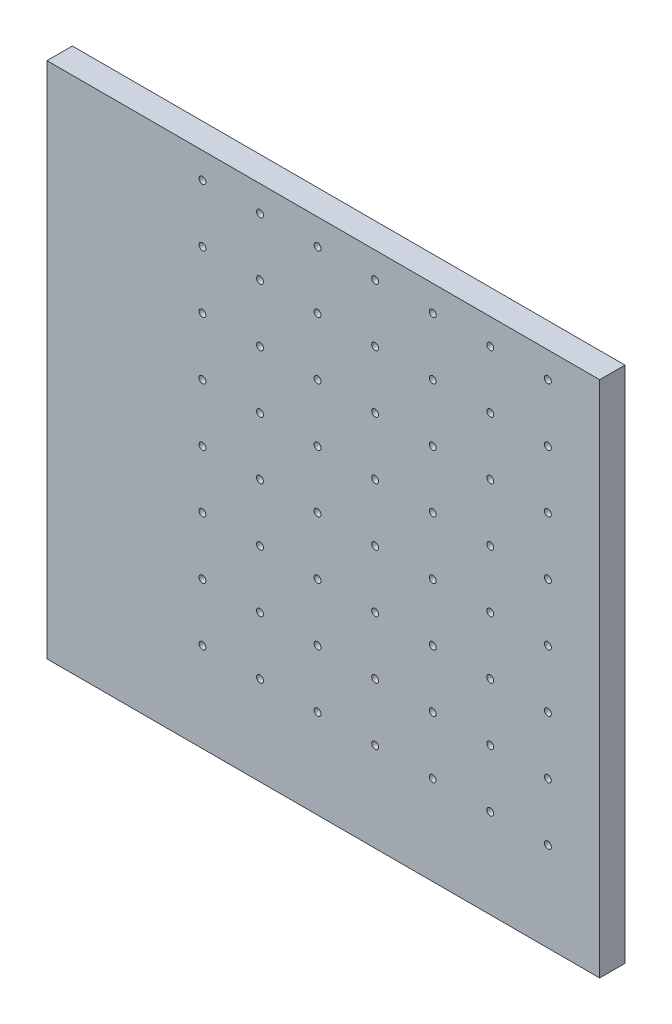
SolidWorks part; units mm, degrees
ref_plane "Front" through (0, 0, 0) normal (0, 0, 1) x (1, 0, 0)
ref_plane "Top" through (0, 0, 0) normal (0, 1, 0) x (1, 0, 0)
ref_plane "Right" through (0, 0, 0) normal (1, 0, 0) x (0, 0, -1)
sketch "Esquisse1" plane through (0, 0, 0) normal (0, 0, 1) x (1, 0, 0)
  line L1 (0, 0) -> (480, 0)
  line L2 (0, 0) -> (0, 450)
  line L3 (0, 450) -> (480, 450)
  line L4 (480, 0) -> (480, 450)
  dimension "D1" = 480
  dimension "D2" = 450
extrude "Boss.-Extru.1" add sketch "Esquisse1" along normal blind 22
sketch "Esquisse2" plane through (0, 0, 22) normal (0, 0, 1) x (1, 0, 0)
  line L0 (260, 115) -> (260, 25) construction
  line L1 (110, 390) -> (410, 390)
  line L2 (110, 390) -> (110, 115)
  line L3 (110, 115) -> (410, 115)
  line L4 (410, 390) -> (410, 115)
  line L5 (0, 0) -> (480, 0) construction
  line L6 (0, 450) -> (0, 0) construction
  line L7 (480, 450) -> (0, 450) construction
  line L8 (480, 0) -> (480, 450) construction
  dimension "D1" = 115
  dimension "D2" = 110
  dimension "D3" = 60
  dimension "D4" = 70
extrude "Enlèv. mat.-Extru.1" cut sketch "Esquisse2" along normal blind 1 from vertex starting at point (0, 450, 0)
sketch "Esquisse3" plane through (0, 0, 0) normal (0, 0, -1) x (-1, 0, 0)
  line L3 (-410, 252.5) -> (-110, 252.5) construction
  line L4 (-410, 115) -> (-410, 390) construction
  line L5 (-110, 390) -> (-110, 115) construction
  line L6 (-360, 252.5) -> (-360, 281.622) construction
  line L7 (-160, 252.5) -> (-160, 281.622) construction
  line L8 (-285, 302.5) -> (-255.5628, 302.5) construction
  line L9 (-160, 352.5) -> (-160, 323.378) construction
  line L10 (-360, 352.5) -> (-360, 323.378) construction
  line L11 (-410, 352.5) -> (-110, 352.5) construction
  line L16 (-314.1888, 402.5) -> (-265.4372, 402.5) construction
  line L17 (-480, 0) -> (-480, 450) construction
  line L18 (0, 0) -> (-480, 0) construction
  circle A0 centre (-435, 277.5) radius 3
  circle A1 centre (-385, 277.5) radius 3
  circle A2 centre (-185, 77.5) radius 3
  circle A3 centre (-135, 77.5) radius 3
  circle A4 centre (-235, 77.5) radius 3
  circle A5 centre (-335, 77.5) radius 3
  circle A6 centre (-335, 277.5) radius 3
  circle A7 centre (-285, 277.5) radius 3
  circle A8 centre (-235, 277.5) radius 3
  circle A9 centre (-285, 77.5) radius 3
  circle A10 centre (-435, 77.5) radius 3
  circle A11 centre (-385, 77.5) radius 3
  circle A12 centre (-185, 277.5) radius 3
  circle A13 centre (-135, 277.5) radius 3
  circle A14 centre (-135, 327.5) radius 3
  circle A15 centre (-185, 327.5) radius 3
  circle A16 centre (-185, 377.5) radius 3
  circle A17 centre (-135, 377.5) radius 3
  circle A18 centre (-235, 377.5) radius 3
  circle A19 centre (-235, 327.5) radius 3
  circle A20 centre (-285, 327.5) radius 3
  circle A21 centre (-335, 327.5) radius 3
  circle A22 centre (-335, 377.5) radius 3
  circle A23 centre (-285, 377.5) radius 3
  circle A24 centre (-435, 377.5) radius 3
  circle A25 centre (-385, 377.5) radius 3
  circle A26 centre (-385, 327.5) radius 3
  circle A27 centre (-435, 327.5) radius 3
  circle A28 centre (-435, 177.5) radius 3
  circle A29 centre (-385, 177.5) radius 3
  circle A30 centre (-385, 127.5) radius 3
  circle A31 centre (-435, 127.5) radius 3
  circle A32 centre (-285, 127.5) radius 3
  circle A33 centre (-335, 127.5) radius 3
  circle A34 centre (-335, 177.5) radius 3
  circle A35 centre (-285, 177.5) radius 3
  circle A36 centre (-235, 177.5) radius 3
  circle A37 centre (-235, 127.5) radius 3
  circle A38 centre (-135, 127.5) radius 3
  circle A39 centre (-185, 127.5) radius 3
  circle A40 centre (-185, 177.5) radius 3
  circle A41 centre (-135, 177.5) radius 3
  circle A42 centre (-135, 227.5) radius 3
  circle A43 centre (-185, 227.5) radius 3
  circle A44 centre (-235, 227.5) radius 3
  circle A45 centre (-285, 227.5) radius 3
  circle A46 centre (-335, 227.5) radius 3
  circle A47 centre (-385, 227.5) radius 3
  circle A48 centre (-435, 227.5) radius 3
  circle A49 centre (-385, 427.5) radius 3
  circle A50 centre (-435, 427.5) radius 3
  circle A51 centre (-285, 427.5) radius 3
  circle A52 centre (-335, 427.5) radius 3
  circle A53 centre (-235, 427.5) radius 3
  circle A54 centre (-135, 427.5) radius 3
  circle A55 centre (-185, 427.5) radius 3
  dimension "D1" = 6
  dimension "D3" = 25
  dimension "D4" = 50
  dimension "D5" = 50
  dimension "D6" = 50
  dimension "D9" = 175
  dimension "D11" = 225
  dimension "D12" = 275
  dimension "D13" = 25
  dimension "D15" = 125
extrude "Enlèv. mat.-Extru.2" cut sketch "Esquisse3" against normal through all
